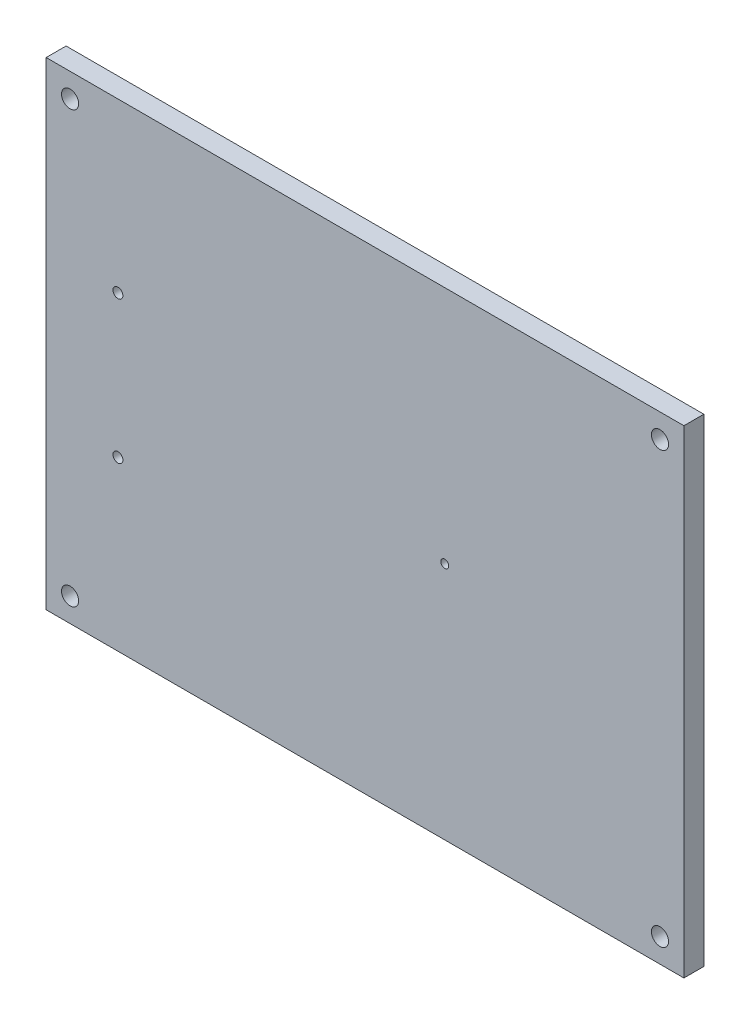
SolidWorks part; units mm, degrees
material "Acrylic (Medium-high impact)"
ref_plane "Front Plane" through (0, 0, 0) normal (0, 0, 1) x (1, 0, 0)
ref_plane "Top Plane" through (0, 0, 0) normal (0, 1, 0) x (1, 0, 0)
ref_plane "Right Plane" through (0, 0, 0) normal (1, 0, 0) x (0, 0, -1)
sketch "Sketch1" plane through (0, 0, 0) normal (0, 0, 1) x (1, 0, 0)
  line L0 (-10, -55) -> (150, -55)
  line L1 (150, -55) -> (150, 65)
  line L2 (150, 65) -> (-10, 65)
  line L3 (-10, 65) -> (-10, -55)
  circle A0 centre (90, 5) radius 1
  circle A1 centre (8, -12.87) radius 1.25
  circle A2 centre (8, 22.87) radius 1.25
  circle A3 centre (-4, -49) radius 2.15
  circle A4 centre (144, -49) radius 2.15
  circle A5 centre (144, 59) radius 2.15
  circle A6 centre (-4, 59) radius 2.15
  dimension "D3" = 2
  dimension "D1" = 160
  dimension "D2" = 120
  dimension "D4" = 100
extrude "Boss-Extrude1" add sketch "Sketch1" along normal blind 5
